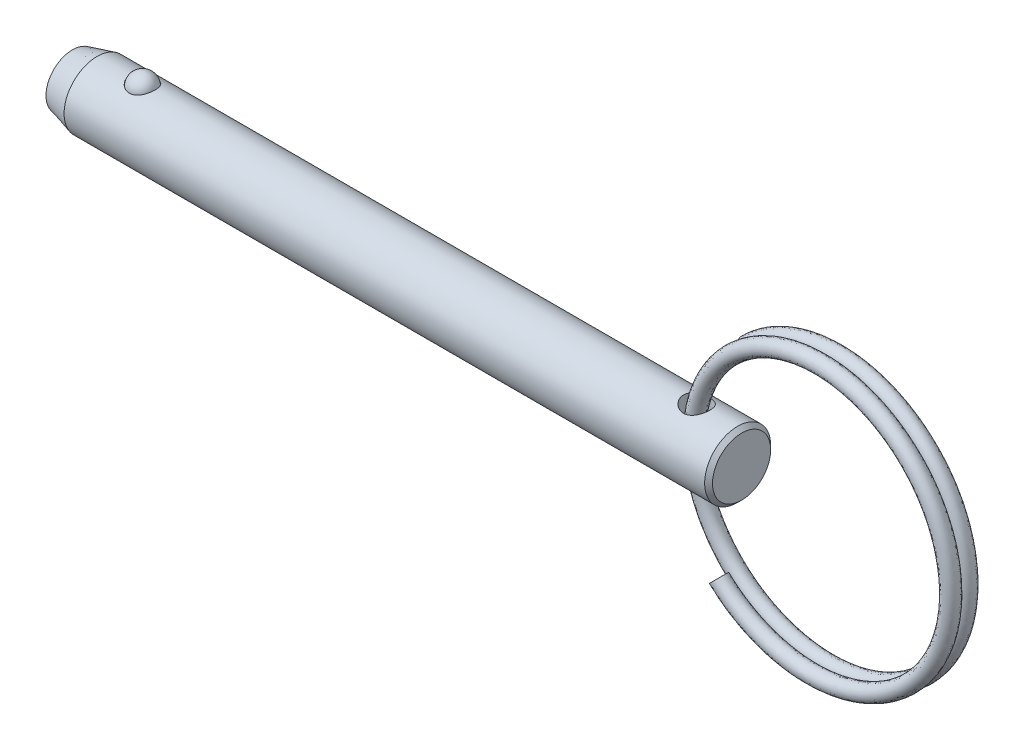
SolidWorks part; units mm, degrees
ref_plane "Front" through (0, 0, 0) normal (0, 0, 1) x (1, 0, 0)
ref_plane "Top" through (0, 0, 0) normal (0, 1, 0) x (1, 0, 0)
ref_plane "Right" through (0, 0, 0) normal (1, 0, 0) x (0, 0, -1)
sketch "Sketch1" plane through (0, 0, 0) normal (0, 0, 1) x (1, 0, 0)
  line L0 (32.1564, 2.794) -> (31.7754, 3.175)
  line L1 (31.7754, 3.175) -> (32.1564, 3.175) construction
  line L4 (32.1564, 2.794) -> (32.1564, 0)
  line L5 (32.1564, 3.175) -> (32.1564, 2.794) construction
  line L16 (31.7754, 3.175) -> (-29.7865, 3.175)
  line L17 (-32.1564, 3.175) -> (-32.1564, 2.54) construction
  line L19 (-29.7865, 3.175) -> (-32.1564, 3.175) construction
  line L22 (-32.1564, -3.175) -> (-29.7865, -3.175) construction
  line L23 (-25.4219, 2.8575) -> (-25.4219, -2.8575) construction
  line L24 (-32.1564, 0) -> (32.1564, 0)
  line L27 (32.1564, 0) -> (34.9504, 0) construction
  line L29 (-32.1564, 0) -> (-32.1564, -2.54) construction
  line L36 (26.5684, 0) -> (26.5684, 3.175) construction
  line L37 (-32.1564, 2.54) -> (-32.1564, 0)
  line L38 (-29.7865, -3.175) -> (32.1564, -3.175) construction
  line L39 (-32.1564, -2.54) -> (-32.1564, -3.175) construction
  line L40 (-29.7865, 3.175) -> (-32.1564, 2.54)
  line L42 (-29.7865, -3.175) -> (-32.1564, -2.54) construction
  line L43 (-29.7865, 3.175) -> (-29.7865, -3.175) construction
  circle A2 centre (-25.4219, 2.8575) radius 1.2319 construction
  point P35 (-24.2316, 3.175)
  dimension "A1" = 15
revolve "Revolve1" add sketch "Sketch1" angle 360 about L27
sketch "Sketch2" plane through (0, 0, 0) normal (0, 0, 1) x (1, 0, 0)
  line L0 (-24.1646, 2.8575) -> (-26.6792, 2.8575)
  line L1 (-25.4219, 4.0894) -> (-25.4219, 4.1148) construction
  line L2 (-24.1646, 2.8575) -> (-21.65, 2.8575) construction
  circle A0 centre (-25.4219, 2.8575) radius 1.2319 construction
  circle A1 centre (-25.4219, 2.8575) radius 1.2319 construction
  arc A2 (-26.6792, 2.8575) -> (-24.1646, 2.8575) centre (-25.4219, 2.8575) cw
  dimension "D1" = 0.0254
revolve "Cut-Revolve1" cut sketch "Sketch2" angle 360 about L2
sketch "Sketch3" plane through (0, 0, 0) normal (0, 0, 1) x (1, 0, 0)
  line L0 (-24.19, 2.8575) -> (-26.6538, 2.8575)
  line L1 (-24.19, 2.8575) -> (-21.7262, 2.8575) construction
  circle A0 centre (-25.4219, 2.8575) radius 1.2319 construction
  arc A1 (-24.19, 2.8575) -> (-26.6538, 2.8575) centre (-25.4219, 2.8575) ccw
revolve "Revolve2" add sketch "Sketch3" angle 360 about L1
sketch "Sketch4" plane through (0, 0, 0) normal (0, 0, 1) x (1, 0, 0)
  line L1 (27.8384, -3.175) -> (29.1084, -3.175)
  line L2 (27.8384, -3.175) -> (27.8384, 3.175)
  line L3 (27.8384, 3.175) -> (29.1084, 3.175)
  line L4 (29.1084, -3.175) -> (29.1084, 3.175)
  line L5 (27.8384, -3.175) -> (27.8384, -4.445) construction
  line L6 (29.1084, 3.175) -> (32.1564, 3.175) construction
  line L8 (26.5684, -3.175) -> (26.5684, 3.175) construction
  line L9 (26.5684, 0) -> (27.8384, 0) construction
  line L11 (27.8384, 0) -> (29.1084, 0) construction
  line L12 (31.7754, 3.175) -> (-29.7865, 3.175) construction
  line L14 (-29.7865, -3.175) -> (32.1564, -3.175) construction
  dimension "D1" = 2.54
revolve "Cut-Revolve2" cut sketch "Sketch4" angle 360 about L2
sketch "Sketch5" plane through (0, 0, 0) normal (0, 0, 1) x (1, 0, 0)
  line L0 (0, 0) -> (26.8614, 0) construction
  line L1 (26.8614, 0) -> (26.8614, 3.175) construction
  line L2 (31.7754, 3.175) -> (-29.7865, 3.175) construction
  line L3 (40.3234, 0) -> (53.7854, 0) construction
  line L4 (29.1084, 3.175) -> (28.8154, 3.175) construction
  line L5 (27.8384, 3.175) -> (29.1084, 3.175) construction
  line L6 (27.2412, 3.175) -> (27.2412, -3.175) construction
  line L7 (26.8614, 3.175) -> (26.5684, 3.175) construction
  line L8 (27.8384, -3.175) -> (29.1084, -3.175) construction
  line L9 (27.2412, -3.175) -> (29.1084, -3.175) construction
  line L10 (26.8614, 0) -> (40.3234, 0) construction
  line L12 (28.8154, 3.175) -> (27.2412, 3.175) construction
  line L13 (40.3234, 11.938) -> (40.3234, 13.462) construction
  circle A0 centre (40.3234, 0) radius 13.462
  circle A1 centre (40.3234, 0) radius 11.938 construction
  circle A2 centre (40.3234, 0) radius 12.7 construction
  point P26 (40.3234, 12.7)
curve "Helix/Spiral1" pitch 1.5494 height 1.3557 radius 13.462 left hand yes centre (40.3234, 0, 0) axis (0, 0, -1) start towards (1, 0, 0)
sketch "Sketch6" plane through (114.0038, 0, 0) normal (0, 1, 0) x (0, 0, -1)
  line L0 (0, 85.6184) -> (0, 86.3804) construction
  line L1 (0, 86.3804) -> (0, 87.1424) construction
  circle A0 centre (0, 86.3804) radius 0.762
  dimension "D1" = 1.524
sketch "Sketch7" plane through (0, 0, 0) normal (0, 0, 1) x (1, 0, 0)
  circle A0 centre (40.3234, 0) radius 13.462 construction
  circle A1 centre (40.3234, 0) radius 13.462
curve "Helix/Spiral2" pitch 1.5494 height 1.3557 radius 13.462 left hand yes centre (40.3234, 0, 0) axis (0, 0, 1) start towards (1, 0, 0)
sweep "Sweep1" add profiles "Sketch6" path "Helix/Spiral1"
sweep "Sweep2" add profiles "Sketch6<2>" path "Helix/Spiral2"
sketch "Sketch6<2>" plane through (114.0038, 0, 0) normal (0, 1, 0) x (0, 0, -1) same geometry as "Sketch6"
equation "\"D12@Sketch1\"=\"A@Sketch1\" * 0.80"
equation "\"D2@Sketch1\"=\"A@Sketch1\" * 0.9"
equation "\"D1@Sketch4\" = \"A@Sketch1\" / 2.5"
equation "\"Ring OD@Sketch5\" = \"R Ring Dia@Sketch5\" * 0.06"
equation "\"D4@Helix/Spiral1\"=\"Ring OD@Sketch5\" + 0.001"
equation "\"D1@Sketch6\"=\"Ring OD@Sketch5\""
equation "\"D4@Helix/Spiral2\" = \"D4@Helix/Spiral1\""
equation "\"D5@Helix/Spiral2\" = \"D5@Helix/Spiral1\""
